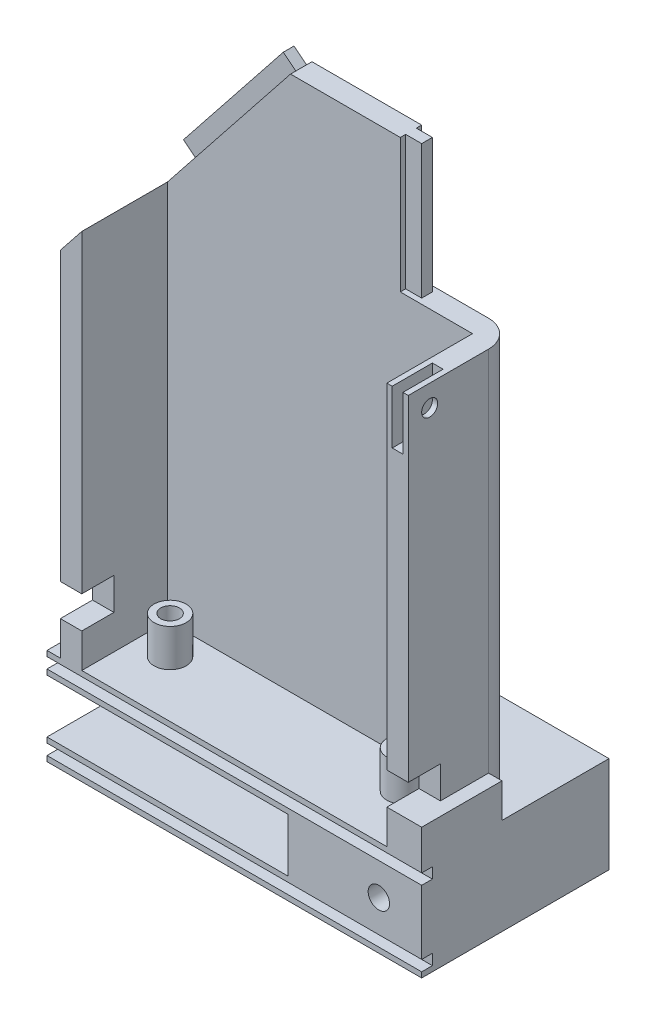
SolidWorks part; units mm, degrees
ref_plane "Front Plane" through (0, 0, 0) normal (0, 0, 1) x (1, 0, 0)
ref_plane "Top Plane" through (0, 0, 0) normal (0, 1, 0) x (1, 0, 0)
ref_plane "Right Plane" through (0, 0, 0) normal (1, 0, 0) x (0, 0, -1)
sketch "Sketch1" plane through (0, 0, 0) normal (0, 1, 0) x (1, 0, 0)
  line L1 (-32.5, -20) -> (32.5, -20)
  line L2 (-32.5, -20) -> (-32.5, 20)
  line L3 (-32.5, 20) -> (32.5, 20)
  line L4 (32.5, -20) -> (32.5, 20)
  line L5 (-32.5, -20) -> (32.5, 20) construction
  line L6 (-32.5, 20) -> (32.5, -20) construction
  point P0 (0, 0)
  dimension "D1" = 65
  dimension "D2" = 40
extrude "Boss-Extrude1" add sketch "Sketch1" along normal blind 100
shell "Shell1" thickness 4 removed face at (0, 0, 0) removed face at (0, 100, 0)
fillet "Fillet1" radius 5 4 edges at (32.5, 50, -20) (32.5, 50, 20) (-32.5, 50, -20) (-32.5, 50, 20)
sketch "Sketch2" plane through (0, 0, 0) normal (0, 0, 1) x (1, 0, 0)
  line L0 (-5.5, 100) -> (-32.5, 66)
  line L1 (28.5, 100) -> (-28.5, 100) construction
  line L2 (-32.5, 100) -> (-32.5, 0) construction
  line L3 (-32.5, 66) -> (-32.5, 100)
  line L4 (-32.5, 100) -> (-5.5, 100)
  dimension "D1" = 5.5
  dimension "D2" = 66
extrude "Cut-Extrude1" cut sketch "Sketch2" against normal through all both and the other way through all
sketch "Sketch3" plane through (0, 0, 0) normal (0, 0, 1) x (1, 0, 0)
  line L1 (32.5, 100) -> (15, 100)
  line L2 (32.5, 100) -> (32.5, 75)
  line L3 (32.5, 75) -> (15, 75)
  line L4 (15, 100) -> (15, 75)
  dimension "D1" = 25
  dimension "D2" = 17.5
extrude "Cut-Extrude2" cut sketch "Sketch3" against normal through all both and the other way through all
sketch "Sketch5" plane through (15, 0, 0) normal (1, 0, 0) x (0, 0, -1)
  line L0 (-18, 100) -> (-18, 75) construction
  line L1 (-16, 100) -> (-20, 100) construction
  line L2 (-16, 75) -> (-20, 75) construction
  line L4 (-19, 100) -> (-17, 100)
  line L5 (-19, 100) -> (-19, 75)
  line L6 (-19, 75) -> (-17, 75)
  line L7 (-17, 100) -> (-17, 75)
  dimension "D1" = 2
extrude "Boss-Extrude2" add sketch "Sketch5" along normal blind 3
mirror "Mirror1" about plane through (0, 0, 0) normal (0, 0, 1) of "Boss-Extrude2"
sketch "Sketch6" plane through (-52.0732, 41.3523, 0) normal (-0.7831, 0.6219, 0) x (0, 0, 1)
  line L0 (-18, 74.8907) -> (-18, 44.8907) construction
  line L1 (-20, 74.8907) -> (-16, 74.8907) construction
  line L3 (-19, 74.8907) -> (-17, 74.8907)
  line L4 (-19, 74.8907) -> (-19, 44.8907)
  line L5 (-19, 44.8907) -> (-17, 44.8907)
  line L6 (-17, 74.8907) -> (-17, 44.8907)
  dimension "D1" = 30
  dimension "D2" = 2
extrude "Boss-Extrude3" add sketch "Sketch6" along normal blind 3
mirror "Mirror2" about plane through (0, 0, 0) normal (0, 0, 1) of "Boss-Extrude3"
sketch "Sketch8" plane through (0, 0, 0) normal (0, 1, 0) x (1, 0, 0)
  line L1 (-35, -35) -> (35, -35)
  line L2 (-35, -35) -> (-35, 35)
  line L3 (-35, 35) -> (35, 35)
  line L4 (35, -35) -> (35, 35)
  line L5 (-35, -35) -> (35, 35) construction
  line L6 (-35, 35) -> (35, -35) construction
  point P0 (0, 0)
  dimension "D1" = 70
  dimension "D2" = 70
extrude "Boss-Extrude4" add sketch "Sketch8" against normal blind 18
sketch "Sketch10" plane through (-35, 0, 0) normal (-1, 0, 0) x (0, 0, 1)
  line L0 (-35, -9) -> (35, -9) construction
  line L1 (-30, -14) -> (30, -14)
  line L2 (-30, -14) -> (-30, -4)
  line L3 (-30, -4) -> (30, -4)
  line L4 (30, -14) -> (30, -4)
  line L5 (-30, -14) -> (30, -4) construction
  line L6 (-30, -4) -> (30, -14) construction
  line L7 (-35, -18) -> (-35, 0) construction
  line L8 (35, -18) -> (35, 0) construction
  line L9 (0, 0) -> (0, -18) construction
  line L10 (-35, -18) -> (35, -18) construction
  point P0 (0, -9)
  dimension "D1" = 60
  dimension "D2" = 10
extrude "Cut-Extrude4" cut sketch "Sketch10" against normal blind 45
sketch "Sketch23" plane through (0, 75, 0) normal (0, 1, 0) x (1, 0, 0)
  line L0 (0, 0) -> (32.5, 0) construction
  line L1 (29.5, 7.5) -> (31.5, 7.5)
  line L2 (29.5, 7.5) -> (29.5, -7.5)
  line L3 (29.5, -7.5) -> (31.5, -7.5)
  line L4 (31.5, 7.5) -> (31.5, -7.5)
  line L5 (32.5, 15) -> (32.5, -15) construction
  line L6 (28.5, 16) -> (28.5, -16) construction
  line L8 (30.5, 14.75) -> (30.5, -14.75) construction
  point P23 (0, 0)
  point P24 (0, 0)
  point P25 (0, 0)
  point P26 (20.5505, -14.75)
  point P27 (23.5, -14.75)
  dimension "D1" = 2
  dimension "D2" = 15
extrude "Cut-Extrude10" cut sketch "Sketch23" against normal blind 10
sketch "Sketch27" plane through (0, 0, 0) normal (0, 1, 0) x (1, 0, 0)
  line L0 (35, -35) -> (35, 35) construction
  line L1 (-35, -35) -> (35, -35)
  line L2 (-35, -35) -> (-35, 0)
  line L3 (-35, 0) -> (35, 0)
  line L4 (35, -35) -> (35, 0)
extrude "Cut-Extrude12" cut sketch "Sketch27" against normal through all both and the other way through all
sketch "Sketch29" plane through (0, 0, 0) normal (0, 0, 1) x (1, 0, 0)
  line L0 (-35, -2) -> (35, -2) construction
  line L1 (-35, -4) -> (-35, 0) construction
  line L2 (35, -18) -> (35, 0) construction
  line L3 (-35, -1) -> (35, -1)
  line L4 (-35, -1) -> (-35, -3)
  line L5 (-35, -3) -> (35, -3)
  line L6 (35, -1) -> (35, -3)
  dimension "D1" = 2
extrude "Cut-Extrude13" cut sketch "Sketch29" against normal blind 2
sketch "Sketch30" plane through (0, 0, 0) normal (0, 0, 1) x (1, 0, 0)
  line L0 (-35, -16) -> (35, -16) construction
  line L1 (-35, -18) -> (-35, -14) construction
  line L2 (35, -18) -> (35, -3) construction
  line L4 (-35, -15) -> (35, -15)
  line L5 (-35, -15) -> (-35, -17)
  line L6 (-35, -17) -> (35, -17)
  line L7 (35, -15) -> (35, -17)
  dimension "D1" = 2
extrude "Cut-Extrude14" cut sketch "Sketch30" against normal blind 2
sketch "Sketch31" plane through (0, 0, 0) normal (0, 0, 1) x (1, 0, 0)
  line L0 (35, -15) -> (35, -3) construction
  line L1 (35, -18) -> (-35, -18) construction
  circle A0 centre (27, -9) radius 2
  dimension "D1" = 4
  dimension "D2" = 8
  dimension "D3" = 9
extrude "Cut-Extrude15" cut sketch "Sketch31" against normal through all both and the other way through all
sketch "Sketch33" plane through (0, 0, -35) normal (0, 0, -1) x (-1, 0, 0)
  circle A0 centre (-27, -9) radius 4
  dimension "D1" = 8
extrude "Cut-Extrude16" cut sketch "Sketch33" against normal blind 15
sketch "Sketch34" plane through (0, 0, 0) normal (0, 1, 0) x (1, 0, 0)
  line L0 (32.5, 0) -> (35, 0) construction
  line L1 (35, 0) -> (35, 35) construction
  circle A0 centre (0, 27.5) radius 1.5
  dimension "D2" = 3
  dimension "D1" = 27.5
  dimension "D3" = 35
extrude "Cut-Extrude17" cut sketch "Sketch34" against normal through all both and the other way through all
sketch "Sketch35" plane through (0, -18, 0) normal (0, -1, 0) x (-1, 0, 0)
  circle A0 centre (0, 27.5) radius 4
  dimension "D1" = 8
extrude "Cut-Extrude18" cut sketch "Sketch35" against normal blind 3
sketch "Sketch39" plane through (0, 0, 0) normal (0, 1, 0) x (1, 0, 0)
  line L0 (-28.5, 0) -> (28.5, 0) construction
  line L2 (28.5, 16) -> (28.5, 0) construction
  circle A0 centre (21, 10.5) radius 3
  point P4 (0, 0)
  dimension "D1" = 6
  dimension "D2" = 10.5
  dimension "D3" = 7.5
extrude "Boss-Extrude7" add sketch "Sketch39" along normal blind 7
sketch "Sketch40" plane through (0, 7, 0) normal (0, 1, 0) x (1, 0, 0)
  circle A0 centre (21, 10.5) radius 1.75
  dimension "D1" = 3.5
extrude "Cut-Extrude20" cut sketch "Sketch40" against normal blind 4
pattern_linear "LPattern4" count 2 spacing 43.5 along (-1, 0, 0) of "Boss-Extrude7", "Cut-Extrude20"
sketch "Sketch41" plane through (32.5, 0, 0) normal (1, 0, 0) x (0, 0, -1)
  line L0 (0, 75) -> (0, 0) construction
  line L1 (6, 6.4) -> (0, 6.4)
  line L2 (6, 6.4) -> (6, 12.4)
  line L3 (6, 12.4) -> (0, 12.4)
  line L4 (0, 6.4) -> (0, 12.4)
  line L5 (0, 0) -> (15, 0) construction
  dimension "D1" = 6.4
  dimension "D2" = 6
  dimension "D3" = 6
extrude "Cut-Extrude21" cut sketch "Sketch41" against normal through all both and the other way through all
sketch "Sketch42" plane through (32.5, 0, 0) normal (1, 0, 0) x (0, 0, -1)
  line L1 (0, 6.4) -> (15, 6.4)
  line L2 (0, 6.4) -> (0, 0)
  line L3 (0, 0) -> (15, 0)
  line L4 (15, 6.4) -> (15, 0)
extrude "Boss-Extrude10" add sketch "Sketch42" along normal up to surface (2.5 mm away) up to face at (35, -9, -6.5)
sketch "Sketch43" plane through (32.5, 0, 0) normal (1, 0, 0) x (0, 0, -1)
  line L0 (0, 75) -> (0, 12.4) construction
  line L1 (15, 75) -> (0, 75) construction
  circle A0 centre (4, 71) radius 1.5
  dimension "D3" = 3
  dimension "D1" = 4
  dimension "D2" = 4
extrude "Cut-Extrude22" cut sketch "Sketch43" against normal blind 10 and the other way through all
